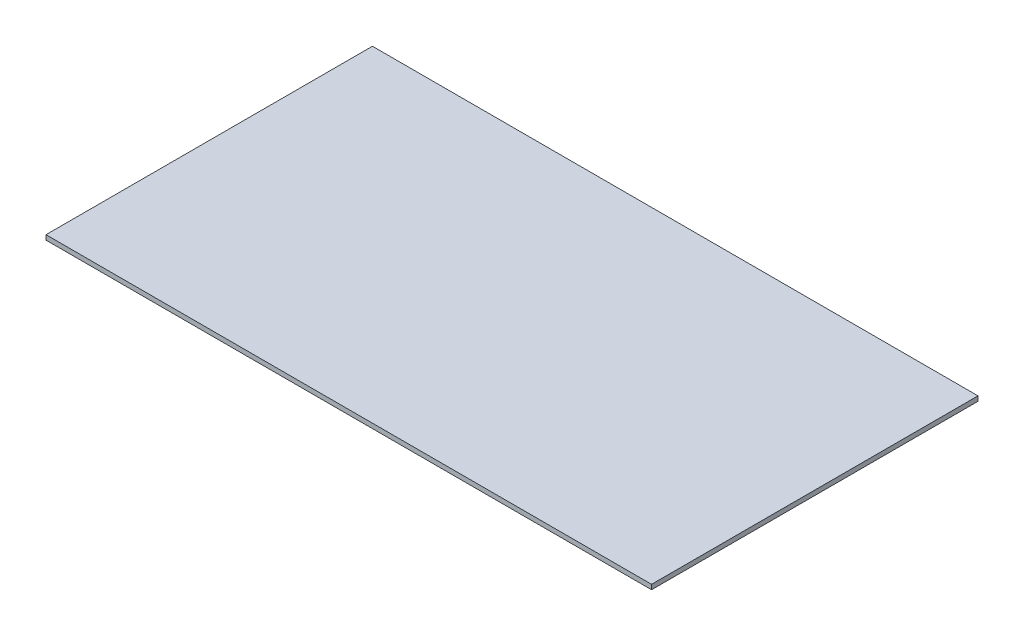
SolidWorks part; units mm, degrees
ref_plane "Front Plane" through (0, 0, 0) normal (0, 0, 1) x (1, 0, 0)
ref_plane "Top Plane" through (0, 0, 0) normal (0, 1, 0) x (1, 0, 0)
ref_plane "Right Plane" through (0, 0, 0) normal (1, 0, 0) x (0, 0, -1)
sketch "Sketch1" plane through (0, 0, 0) normal (0, 1, 0) x (1, 0, 0)
  line L0 (812.8, 3.175) -> (812.8, 434.975) construction
  line L1 (0, 0) -> (812.8, 0)
  line L2 (0, 0) -> (0, 438.15)
  line L3 (0, 438.15) -> (812.8, 438.15)
  line L4 (812.8, 0) -> (812.8, 438.15)
  line L5 (785.749, 438.15) -> (812.8, 438.15) construction
extrude "Boss-Extrude1" add sketch "Sketch1" along normal blind 6.35
